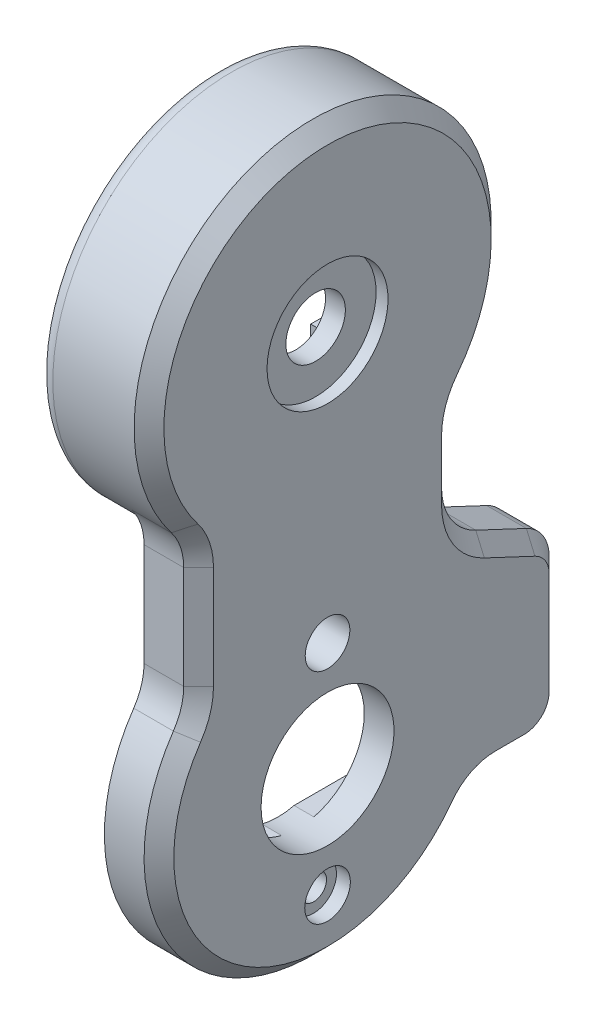
SolidWorks part; units mm, degrees
ref_plane "Front Plane" through (0, 0, 0) normal (0, 0, 1) x (1, 0, 0)
ref_plane "Top Plane" through (0, 0, 0) normal (0, 1, 0) x (1, 0, 0)
ref_plane "Right Plane" through (0, 0, 0) normal (1, 0, 0) x (0, 0, -1)
sketch "Sketch1" plane through (0, 0, 0) normal (1, 0, 0) x (0, 0, -1)
  line L0 (39, 3.3371) -> (39, -7.0385)
  line L1 (68.9482, -28.4) -> (71.85, -28.4)
  line L2 (75.85, -24.4) -> (75.85, -14.1397)
  line L3 (73.5516, -10.5196) -> (68.4476, -8.1205)
  line L4 (65, -2.6905) -> (65, 3.3371)
  arc A0 (66.25, 7.0028) -> (37.75, 7.0028) centre (52, 18) ccw
  arc A1 (37.75, 7.0028) -> (39, 3.3371) centre (33, 3.3371) cw
  arc A2 (39, -7.0385) -> (37.9565, -10.4198) centre (33, -7.0385) cw
  arc A3 (37.9565, -10.4198) -> (65.7199, -30.0381) centre (52, -20) ccw
  arc A4 (65.7199, -30.0381) -> (68.9482, -28.4) centre (68.9482, -32.4) cw
  arc A5 (71.85, -28.4) -> (75.85, -24.4) centre (71.85, -24.4) ccw
  arc A6 (75.85, -14.1397) -> (73.5516, -10.5196) centre (71.85, -14.1397) ccw
  arc A7 (68.4476, -8.1205) -> (65, -2.6905) centre (71, -2.6905) cw
  arc A8 (65, 3.3371) -> (66.25, 7.0028) centre (71, 3.3371) cw
extrude "Boss-Extrude1" add sketch "Sketch1" along normal blind 5.5 from offset 55.1
sketch "Sketch2" plane through (0, 0, 0) normal (1, 0, 0) x (0, 0, -1)
  line L0 (39.8, 3.3371) -> (39.8, -7.0385)
  line L1 (68.9482, -27.6) -> (71.85, -27.6)
  line L2 (75.05, -24.4) -> (75.05, -14.1397)
  line L3 (73.2113, -11.2436) -> (68.1073, -8.8446)
  line L4 (64.2, -2.6905) -> (64.2, 3.3371)
  arc A0 (65.6167, 7.4916) -> (38.3833, 7.4916) centre (52, 18) ccw
  arc A1 (38.3833, 7.4916) -> (39.8, 3.3371) centre (33, 3.3371) cw
  arc A2 (39.8, -7.0385) -> (38.6174, -10.8706) centre (33, -7.0385) cw
  arc A3 (38.6174, -10.8706) -> (65.0743, -29.5657) centre (52, -20) ccw
  arc A4 (65.0743, -29.5657) -> (68.9482, -27.6) centre (68.9482, -32.4) cw
  arc A5 (71.85, -27.6) -> (75.05, -24.4) centre (71.85, -24.4) ccw
  arc A6 (75.05, -14.1397) -> (73.2113, -11.2436) centre (71.85, -14.1397) ccw
  arc A7 (68.1073, -8.8446) -> (64.2, -2.6905) centre (71, -2.6905) cw
  arc A8 (64.2, 3.3371) -> (65.6167, 7.4916) centre (71, 3.3371) cw
extrude "Boss-Extrude2" add sketch "Sketch2" along normal blind 0.6 from offset 55 separate body
combine bodies "Combine1" operation type subtract main body 101 bodies to subtract 102
sketch "Sketch3" plane through (0, 0, 0) normal (1, 0, 0) x (0, 0, -1)
  circle A0 centre (52, 18) radius 18
  circle A1 centre (52, 18) radius 16.3
extrude "Boss-Extrude3" add sketch "Sketch3" along normal blind 6.2 from offset 49.4
chamfer "Chamfer1" distance 1.5 angle 45 14 edges at (60.6, -5.9065, -65.9347) (60.6, 0.3233, -65) (60.6, -9.3201, -70.9996) (60.6, 5.2736, -65.3211) (60.6, -11.9956, -75.2269) (60.6, 36, -52) (60.6, -19.2698, -75.85) (60.6, 5.2736, -38.6789) (60.6, -27.2284, -74.6784) (60.6, -1.8507, -39) (60.6, -28.4, -70.3991) (60.6, -8.8078, -38.7332) (60.6, -28.833, -67.1381) (60.6, -33.8836, -42.1895)
fillet "Fillet1" radius 1.5 1 edges at (49.4, 18, -70)
sketch "Sketch4" plane through (0, 0, 0) normal (0, 0, 1) x (1, 0, 0)
  line L1 (55.1, 6.5) -> (57.4, 6.5)
  line L2 (55.1, 6.5) -> (55.1, 29.5)
  line L3 (55.1, 29.5) -> (57.4, 29.5)
  line L4 (57.4, 6.5) -> (57.4, 29.5)
extrude "Boss-Extrude4" add sketch "Sketch4" along normal blind 6.6 from offset 55.3 separate body offset against normal yes
combine bodies "Combine2" operation type subtract main body 104 bodies to subtract 105
sketch "Sketch5" plane through (0, 0, 0) normal (0, 0, 1) x (1, 0, 0)
  line L1 (55.1, 14.7) -> (57.4, 14.7)
  line L2 (55.1, 14.7) -> (55.1, 21.3)
  line L3 (55.1, 21.3) -> (57.4, 21.3)
  line L4 (57.4, 14.7) -> (57.4, 21.3)
extrude "Boss-Extrude5" add sketch "Sketch5" along normal blind 23 from offset 63.5 separate body offset against normal yes
combine bodies "Combine3" operation type subtract main body 106 bodies to subtract 107
sketch "Sketch6" plane through (0, 0, 0) normal (1, 0, 0) x (0, 0, -1)
  circle A0 centre (52, 18) radius 4.6
extrude "Boss-Extrude6" add sketch "Sketch6" along normal blind 2.3 from offset 55.1 separate body
combine bodies "Combine4" operation type subtract main body 108 bodies to subtract 109
sketch "Sketch7" plane through (0, 0, 0) normal (1, 0, 0) x (0, 0, -1)
  circle A0 centre (52, 18) radius 6.1
extrude "Boss-Extrude7" add sketch "Sketch7" along normal blind 1.7 from offset 59.4 separate body
combine bodies "Combine5" operation type subtract main body 110 bodies to subtract 111
sketch "Sketch8" plane through (0, 0, 0) normal (1, 0, 0) x (0, 0, -1)
  circle A0 centre (52, 18) radius 3
extrude "Boss-Extrude8" add sketch "Sketch8" along normal blind 2.2 from offset 57.3 separate body
combine bodies "Combine6" operation type subtract main body 112 bodies to subtract 113
sketch "Sketch9" plane through (0, 0, 0) normal (0, 0, 1) x (1, 0, 0)
  line L1 (57.3, 24.6) -> (59.6, 24.6)
  line L2 (57.3, 24.6) -> (57.3, 28)
  line L3 (57.3, 28) -> (59.6, 28)
  line L4 (59.6, 24.6) -> (59.6, 28)
extrude "Boss-Extrude9" add sketch "Sketch9" along normal blind 1.8 from offset 52.9 separate body offset against normal yes
combine bodies "Combine7" operation type subtract main body 114 bodies to subtract 115
sketch "Sketch10" plane through (0, 0, 0) normal (0, 0, 1) x (1, 0, 0)
  line L1 (57.3, 17.1) -> (59.6, 17.1)
  line L2 (57.3, 17.1) -> (57.3, 18.9)
  line L3 (57.3, 18.9) -> (59.6, 18.9)
  line L4 (59.6, 17.1) -> (59.6, 18.9)
extrude "Boss-Extrude10" add sketch "Sketch10" along normal blind 3.4 from offset 62 separate body offset against normal yes
combine bodies "Combine8" operation type subtract main body 116 bodies to subtract 117
sketch "Sketch11" plane through (0, 0, 0) normal (0, 0, 1) x (1, 0, 0)
  line L1 (57.3, 8) -> (59.6, 8)
  line L2 (57.3, 8) -> (57.3, 11.4)
  line L3 (57.3, 11.4) -> (59.6, 11.4)
  line L4 (59.6, 8) -> (59.6, 11.4)
extrude "Boss-Extrude11" add sketch "Sketch11" along normal blind 1.8 from offset 52.9 separate body offset against normal yes
combine bodies "Combine9" operation type subtract main body 118 bodies to subtract 119
sketch "Sketch12" plane through (0, 0, 0) normal (0, 0, 1) x (1, 0, 0)
  line L1 (57.3, 17.1) -> (59.6, 17.1)
  line L2 (57.3, 17.1) -> (57.3, 18.9)
  line L3 (57.3, 18.9) -> (59.6, 18.9)
  line L4 (59.6, 17.1) -> (59.6, 18.9)
extrude "Boss-Extrude12" add sketch "Sketch12" along normal blind 3.4 from offset 45.4 separate body offset against normal yes
combine bodies "Combine10" operation type subtract main body 120 bodies to subtract 121
sketch "Sketch13" plane through (0, 0, 0) normal (0, 0, 1) x (1, 0, 0)
  line L1 (49.3, -0.6) -> (55.6, -0.6)
  line L2 (49.3, -0.6) -> (49.3, 2.4984)
  line L3 (49.3, 2.4984) -> (55.6, 2.4984)
  line L4 (55.6, -0.6) -> (55.6, 2.4984)
extrude "Boss-Extrude13" add sketch "Sketch13" along normal blind 8 from offset 56 separate body offset against normal yes
combine bodies "Combine11" operation type subtract main body 122 bodies to subtract 123
sketch "Sketch14" plane through (0, 0, 0) normal (0, 0, 1) x (1, 0, 0)
  line L1 (55.5, -21) -> (59.6, -21)
  line L2 (55.5, -21) -> (55.5, -19)
  line L3 (55.5, -19) -> (59.6, -19)
  line L4 (59.6, -21) -> (59.6, -19)
extrude "Boss-Extrude14" add sketch "Sketch14" along normal blind 2.9 from offset 44.775 separate body offset against normal yes
combine bodies "Combine12" operation type subtract main body 124 bodies to subtract 125
sketch "Sketch15" plane through (0, 0, 0) normal (0, 0, 1) x (1, 0, 0)
  line L1 (55.5, -21) -> (59.6, -21)
  line L2 (55.5, -21) -> (55.5, -19)
  line L3 (55.5, -19) -> (59.6, -19)
  line L4 (59.6, -21) -> (59.6, -19)
extrude "Boss-Extrude15" add sketch "Sketch15" along normal blind 2.9 from offset 72.925 separate body offset against normal yes
combine bodies "Combine13" operation type subtract main body 126 bodies to subtract 127
sketch "Sketch16" plane through (0, 0, 0) normal (0, 0, 1) x (1, 0, 0)
  line L1 (55.5, -26.5) -> (57.6, -26.5)
  line L2 (55.5, -26.5) -> (55.5, -13.5)
  line L3 (55.5, -13.5) -> (57.6, -13.5)
  line L4 (57.6, -26.5) -> (57.6, -13.5)
extrude "Boss-Extrude16" add sketch "Sketch16" along normal blind 23.4 from offset 69.1 separate body offset against normal yes
combine bodies "Combine14" operation type subtract main body 128 bodies to subtract 129
sketch "Sketch17" plane through (0, 0, 0) normal (1, 0, 0) x (0, 0, -1)
  circle A0 centre (52, -20) radius 6.7
extrude "Boss-Extrude17" add sketch "Sketch17" along normal blind 5.6 from offset 55.5 separate body
combine bodies "Combine15" operation type subtract main body 130 bodies to subtract 131
sketch "Sketch18" plane through (0, 0, 0) normal (1, 0, 0) x (0, 0, -1)
  circle A0 centre (52, -9) radius 2.25
extrude "Boss-Extrude18" add sketch "Sketch18" along normal blind 5.6 from offset 55.5 separate body
combine bodies "Combine16" operation type subtract main body 132 bodies to subtract 133
sketch "Sketch19" plane through (0, 0, 0) normal (1, 0, 0) x (0, 0, -1)
  circle A0 centre (52, -31) radius 2.3
extrude "Boss-Extrude19" add sketch "Sketch19" along normal blind 1.9 from offset 59.2 separate body
combine bodies "Combine17" operation type subtract main body 134 bodies to subtract 135
sketch "Sketch20" plane through (0, 0, 0) normal (1, 0, 0) x (0, 0, -1)
  circle A0 centre (52, -31) radius 1.3
extrude "Boss-Extrude20" add sketch "Sketch20" along normal blind 3.75 from offset 55.5 separate body
combine bodies "Combine18" operation type subtract main body 136 bodies to subtract 137
sketch "Sketch21" plane through (0, 0, 0) normal (0, 0, 1) x (1, 0, 0)
  line L1 (55.5, -6.05) -> (58.6, -6.05)
  line L2 (55.5, -6.05) -> (55.5, -1.95)
  line L3 (55.5, -1.95) -> (58.6, -1.95)
  line L4 (58.6, -6.05) -> (58.6, -1.95)
extrude "Boss-Extrude21" add sketch "Sketch21" along normal blind 2.2 from offset 44.6 separate body offset against normal yes
combine bodies "Combine19" operation type subtract main body 138 bodies to subtract 139
sketch "Sketch22" plane through (0, 0, 0) normal (0, 1, 0) x (1, 0, 0)
  line L0 (58.8, 44) -> (58.8, 43)
  line L1 (58.8, 43) -> (52.8, 43)
  line L2 (52.8, 43) -> (52.8, 42.6)
  line L3 (52.8, 42.6) -> (52.2, 42.6)
  line L4 (52.2, 42.6) -> (51.4, 43.4)
  line L5 (51.4, 43.4) -> (51.4, 44)
  line L6 (51.4, 44) -> (58.8, 44)
extrude "Boss-Extrude22" add sketch "Sketch22" along normal blind 3.5 from offset 5.75 offset against normal yes
sketch "Sketch23" plane through (0, 0, 0) normal (0, 0, 1) x (1, 0, 0)
  line L1 (55.5, -6.05) -> (58.6, -6.05)
  line L2 (55.5, -6.05) -> (55.5, -1.95)
  line L3 (55.5, -1.95) -> (58.6, -1.95)
  line L4 (58.6, -6.05) -> (58.6, -1.95)
extrude "Boss-Extrude23" add sketch "Sketch23" along normal blind 2.2 from offset 61.6 separate body offset against normal yes
combine bodies "Combine20" operation type subtract main body 141 bodies to subtract 142
sketch "Sketch24" plane through (0, 0, 0) normal (0, 1, 0) x (1, 0, 0)
  line L0 (58.8, 60) -> (58.8, 61)
  line L1 (58.8, 61) -> (52.8, 61)
  line L2 (52.8, 61) -> (52.8, 61.4)
  line L3 (52.8, 61.4) -> (52.2, 61.4)
  line L4 (52.2, 61.4) -> (51.4, 60.6)
  line L5 (51.4, 60.6) -> (51.4, 60)
  line L6 (51.4, 60) -> (58.8, 60)
extrude "Boss-Extrude24" add sketch "Sketch24" along normal blind 3.5 from offset 5.75 offset against normal yes
